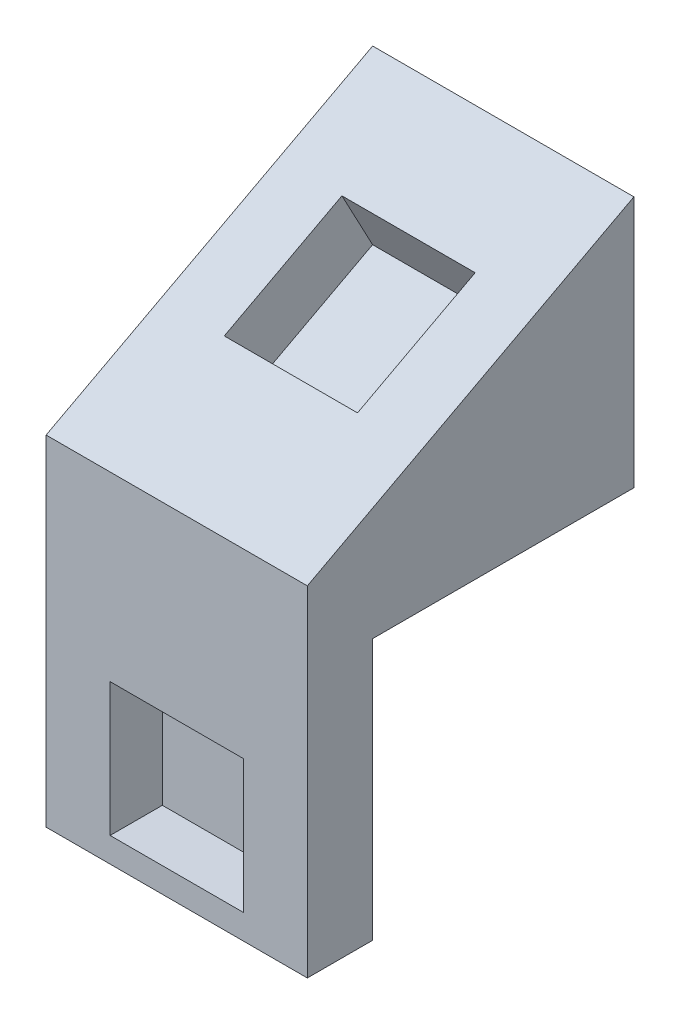
SolidWorks part; units mm, degrees
ref_plane "Płaszczyzna przednia" through (0, 0, 0) normal (0, 0, 1) x (1, 0, 0)
ref_plane "Płaszczyzna górna" through (0, 0, 0) normal (0, 1, 0) x (1, 0, 0)
ref_plane "Płaszczyzna prawa" through (0, 0, 0) normal (1, 0, 0) x (0, 0, -1)
sketch "Szkic1" plane through (0, 0, 0) normal (0, 0, 1) x (1, 0, 0)
  line L1 (-10, -13) -> (10, -13)
  line L2 (-10, -13) -> (-10, 13)
  line L3 (-10, 13) -> (10, 13)
  line L4 (10, -13) -> (10, 13)
  line L5 (-10, -13) -> (10, 13) construction
  line L6 (-10, 13) -> (10, -13) construction
  point P0 (0, 0)
  dimension "D1" = 26
  dimension "D2" = 20
extrude "Dodanie-wyciągnięcie1" add sketch "Szkic1" along normal blind 5
sketch "Szkic2" plane through (0, 0, 0) normal (0, 0, -1) x (-1, 0, 0)
  line L1 (10, 13) -> (-10, 13)
  line L2 (10, 13) -> (10, 7)
  line L3 (10, 7) -> (-10, 7)
  line L4 (-10, 13) -> (-10, 7)
  line L5 (-10, -13) -> (-10, 13) construction
  dimension "D1" = 6
  dimension "D2" = 20
extrude "Dodanie-wyciągnięcie2" add sketch "Szkic2" along normal blind 20
sketch "Szkic3" plane through (0, 0, 5) normal (0, 0, 1) x (1, 0, 0)
  line L0 (10, 13) -> (-10, 13) construction
  line L1 (-5.1, -11.1) -> (5.1, -11.1)
  line L2 (-5.1, -11.1) -> (-5.1, -0.9)
  line L3 (-5.1, -0.9) -> (5.1, -0.9)
  line L4 (5.1, -11.1) -> (5.1, -0.9)
  line L5 (-5.1, -11.1) -> (5.1, -0.9) construction
  line L6 (-5.1, -0.9) -> (5.1, -11.1) construction
  line L7 (-10, -13) -> (10, -13) construction
  point P0 (0, -6)
  point P7 (0, 13)
  dimension "D1" = 10.2
  dimension "D2" = 7
extrude "Wytnij-wyciągnięcie1" cut sketch "Szkic3" against normal blind 4
sketch "Szkic4" plane through (10, 0, 0) normal (1, 0, 0) x (0, 0, -1)
  line L0 (-5, 13) -> (20, 26.2927)
  line L1 (-5, 13) -> (20, 13) construction
  line L2 (20, 26.2927) -> (20, 13)
  line L3 (20, 13) -> (-5, 13)
  line L4 (-5, -13) -> (-5, 13) construction
  dimension "D1" = 28
extrude "Dodanie-wyciągnięcie3" add sketch "Szkic4" against normal up to surface (20 mm away) up to face at (-10, 2.3333, -5)
sketch "Szkic5" plane through (0, 12.2073, 6.4908) normal (0, 0.8829, 0.4695) x (1, 0, 0)
  line L0 (10, 1.6884) -> (-10, 1.6884) construction
  line L1 (-5.1, 11.5884) -> (5.1, 11.5884)
  line L2 (-5.1, 11.5884) -> (-5.1, 21.7884)
  line L3 (-5.1, 21.7884) -> (5.1, 21.7884)
  line L4 (5.1, 11.5884) -> (5.1, 21.7884)
  line L5 (-5.1, 11.5884) -> (5.1, 21.7884) construction
  line L6 (-5.1, 21.7884) -> (5.1, 11.5884) construction
  point P0 (0, 16.6884)
  dimension "D1" = 10.2
  dimension "D2" = 15
extrude "Wytnij-wyciągnięcie2" cut sketch "Szkic5" against normal blind 5
sketch "Szkic6" plane through (0, 0, -20) normal (0, 0, -1) x (-1, 0, 0)
  line L0 (-10, 7) -> (10, 7) construction
  circle A0 centre (0, 13) radius 2
  point P4 (0, 7)
  dimension "D1" = 4
  dimension "D2" = 6
extrude "Wytnij-wyciągnięcie3" cut sketch "Szkic6" against normal blind 8
